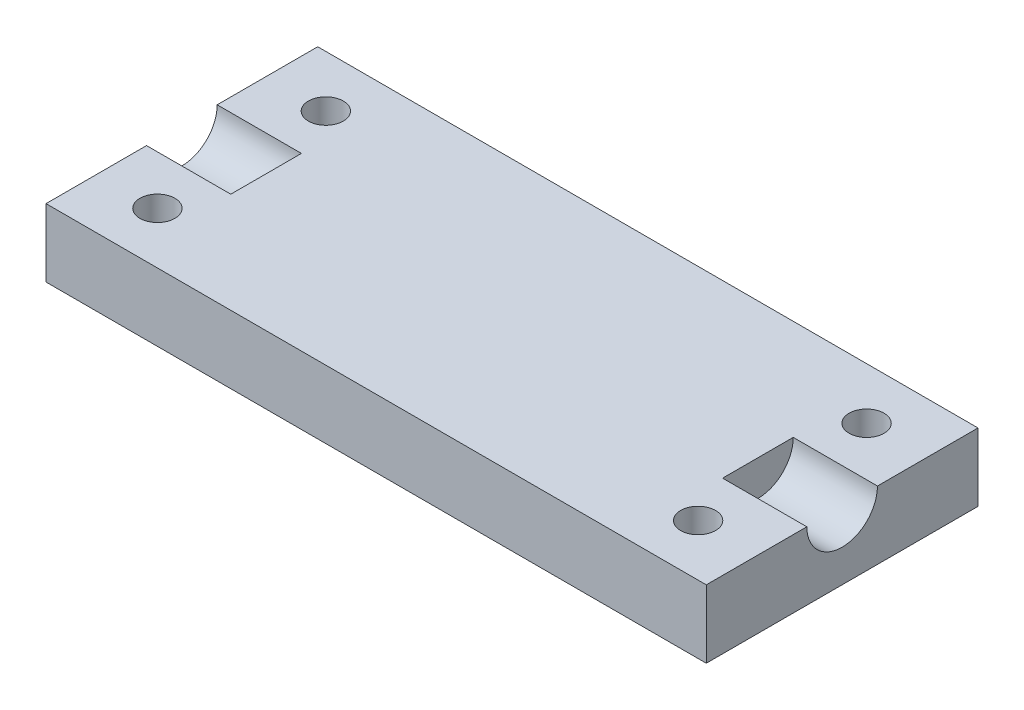
SolidWorks part; units mm, degrees
ref_plane "Front Plane" through (0, 0, 0) normal (0, 0, 1) x (1, 0, 0)
ref_plane "Top Plane" through (0, 0, 0) normal (0, 1, 0) x (1, 0, 0)
ref_plane "Right Plane" through (0, 0, 0) normal (1, 0, 0) x (0, 0, -1)
sketch "Sketch1" plane through (0, 0, 0) normal (0, 1, 0) x (1, 0, 0)
  line L1 (-30.861, -12.7) -> (30.861, -12.7)
  line L2 (-30.861, -12.7) -> (-30.861, 12.7)
  line L3 (-30.861, 12.7) -> (30.861, 12.7)
  line L4 (30.861, -12.7) -> (30.861, 12.7)
  line L5 (-30.861, -12.7) -> (30.861, 12.7) construction
  line L6 (-30.861, 12.7) -> (30.861, -12.7) construction
  point P0 (0, 0)
  dimension "D1" = 61.722
  dimension "D2" = 25.4
extrude "Boss-Extrude1" add sketch "Sketch1" against normal blind 6.35
sketch "Sketch2" plane through (30.861, 0, 0) normal (1, 0, 0) x (0, 0, -1)
  line L0 (-12.7, 0) -> (12.7, 0) construction
  circle A0 centre (0, 0) radius 3.302
  dimension "D1" = 6.604
extrude "Cut-Extrude1" cut sketch "Sketch2" against normal blind 7.874
sketch "Sketch3" plane through (-30.861, 0, 0) normal (-1, 0, 0) x (0, 0, 1)
  circle A0 centre (0, 0) radius 3.302
  dimension "D1" = 6.604
extrude "Cut-Extrude2" cut sketch "Sketch3" against normal blind 7.874
sketch "Sketch4" plane through (0, 0, 0) normal (0, 1, 0) x (1, 0, 0)
  line L0 (-30.861, -3.302) -> (-30.861, -12.7) construction
  line L1 (-30.861, 12.7) -> (-30.861, 3.302) construction
  line L2 (30.861, 3.302) -> (30.861, 12.7) construction
  line L3 (30.861, -12.7) -> (30.861, -3.302) construction
  line L4 (30.861, 12.7) -> (-30.861, 12.7) construction
  line L5 (-30.861, -12.7) -> (30.861, -12.7) construction
  circle A0 centre (25.273, -7.874) radius 1.632
  circle A1 centre (25.273, 7.874) radius 1.632
  circle A2 centre (-25.273, 7.874) radius 1.632
  circle A3 centre (-25.273, -7.874) radius 1.632
  dimension "D1" = 3.2639
  dimension "D2" = 3.2639
  dimension "D3" = 3.2639
  dimension "D4" = 3.2639
  dimension "D5" = 5.588
  dimension "D6" = 5.588
  dimension "D7" = 5.588
  dimension "D8" = 5.588
  dimension "D9" = 4.826
  dimension "D10" = 4.826
  dimension "D11" = 4.826
  dimension "D12" = 4.826
extrude "Cut-Extrude11" cut sketch "Sketch4" against normal up to next
